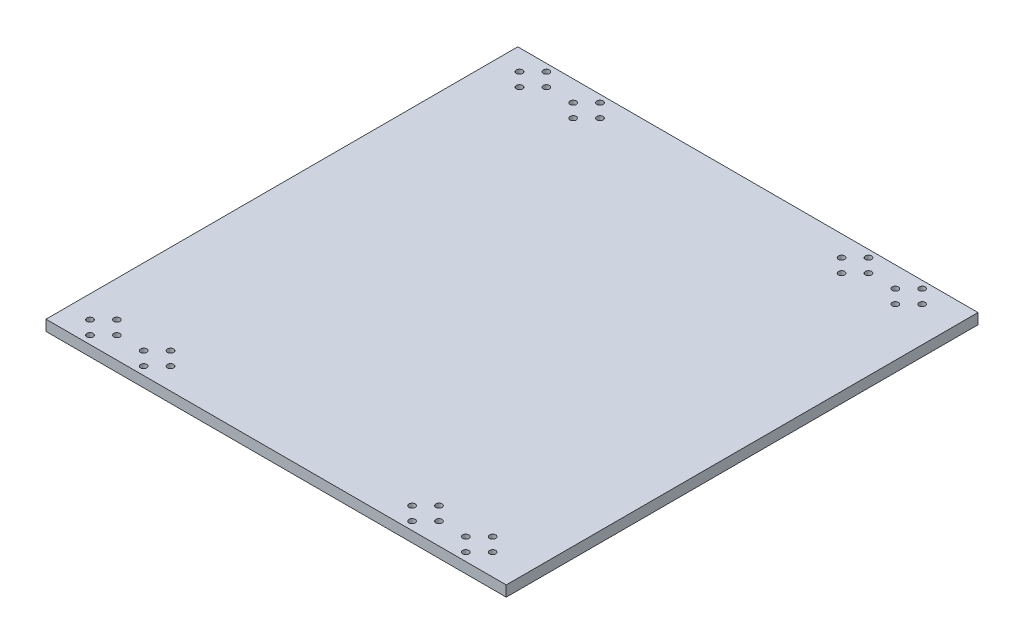
SolidWorks part; units mm, degrees
ref_plane "Front Plane" through (0, 0, 0) normal (0, 0, 1) x (1, 0, 0)
ref_plane "Top Plane" through (0, 0, 0) normal (0, 1, 0) x (1, 0, 0)
ref_plane "Right Plane" through (0, 0, 0) normal (1, 0, 0) x (0, 0, -1)
sketch "Sketch1" plane through (0, 0, 0) normal (0, 1, 0) x (1, 0, 0)
  line L1 (-132.0925, 92.3972) -> (142.2275, 92.3972)
  line L2 (-132.0925, 92.3972) -> (-132.0925, -195.6388)
  line L3 (-132.0925, -195.6388) -> (142.2275, -195.6388)
  line L4 (142.2275, 92.3972) -> (142.2275, -195.6388)
  dimension "D1" = 274.32
  dimension "D2" = 288.036
extrude "Boss-Extrude1" add sketch "Sketch1" along normal blind 6.35
sketch "Sketch2" plane through (0, 0, 0) normal (0, -1, 0) x (1, 0, 0)
  circle A0 centre (121.2775, -76.3612) radius 1.85 construction
  circle A1 centre (105.2775, -76.3612) radius 1.85 construction
  circle A2 centre (113.2775, -84.3612) radius 1.85 construction
  circle A3 centre (113.2775, -68.3612) radius 1.85 construction
  circle A4 centre (121.2775, -76.3612) radius 1.85
  circle A5 centre (105.2775, -76.3612) radius 1.85
  circle A6 centre (113.2775, -84.3612) radius 1.85
  circle A7 centre (113.2775, -68.3612) radius 1.85
  circle A8 centre (89.2775, -76.3612) radius 1.85 construction
  circle A9 centre (89.2775, -76.3612) radius 1.85
  circle A10 centre (81.2775, -84.3612) radius 1.85 construction
  circle A11 centre (81.2775, -84.3612) radius 1.85
  circle A12 centre (81.2775, -68.3612) radius 1.85 construction
  circle A13 centre (81.2775, -68.3612) radius 1.85
  circle A14 centre (73.2775, -76.3612) radius 1.85 construction
  circle A15 centre (73.2775, -76.3612) radius 1.85
  circle A16 centre (-86.7225, -76.3612) radius 1.85 construction
  circle A17 centre (-118.7225, -76.3612) radius 1.85 construction
  circle A18 centre (-110.7225, -84.3612) radius 1.85 construction
  circle A19 centre (-102.7225, -76.3612) radius 1.85 construction
  circle A20 centre (-110.7225, -68.3612) radius 1.85 construction
  circle A21 centre (-86.7225, -76.3612) radius 1.85
  circle A22 centre (-118.7225, -76.3612) radius 1.85
  circle A23 centre (-110.7225, -84.3612) radius 1.85
  circle A24 centre (-102.7225, -76.3612) radius 1.85
  circle A25 centre (-110.7225, -68.3612) radius 1.85
  circle A26 centre (-70.7225, -76.3612) radius 1.85 construction
  circle A27 centre (-78.7225, -68.3612) radius 1.85 construction
  circle A28 centre (-78.7225, -84.3612) radius 1.85 construction
  circle A29 centre (-86.7225, -76.3612) radius 1.85
  circle A30 centre (-70.7225, -76.3612) radius 1.85
  circle A31 centre (-78.7225, -68.3612) radius 1.85
  circle A32 centre (-78.7225, -84.3612) radius 1.85
  circle A33 centre (73.2775, 179.6388) radius 1.85 construction
  circle A34 centre (81.2775, 187.6388) radius 1.85 construction
  circle A35 centre (81.2775, 171.6388) radius 1.85 construction
  circle A36 centre (89.2775, 179.6388) radius 1.85 construction
  circle A37 centre (105.2775, 179.6388) radius 1.85 construction
  circle A38 centre (113.2775, 187.6388) radius 1.85 construction
  circle A39 centre (121.2775, 179.6388) radius 1.85 construction
  circle A40 centre (113.2775, 171.6388) radius 1.85 construction
  circle A41 centre (73.2775, 179.6388) radius 1.85
  circle A42 centre (81.2775, 187.6388) radius 1.85
  circle A43 centre (81.2775, 171.6388) radius 1.85
  circle A44 centre (89.2775, 179.6388) radius 1.85
  circle A45 centre (105.2775, 179.6388) radius 1.85
  circle A46 centre (113.2775, 187.6388) radius 1.85
  circle A47 centre (121.2775, 179.6388) radius 1.85
  circle A48 centre (113.2775, 171.6388) radius 1.85
  circle A49 centre (-70.7225, 179.6388) radius 1.85 construction
  circle A50 centre (-78.7225, 187.6388) radius 1.85 construction
  circle A51 centre (-78.7225, 171.6388) radius 1.85 construction
  circle A52 centre (-86.7225, 179.6388) radius 1.85 construction
  circle A53 centre (-102.7225, 179.6388) radius 1.85 construction
  circle A54 centre (-110.7225, 187.6388) radius 1.85 construction
  circle A55 centre (-118.7225, 179.6388) radius 1.85 construction
  circle A56 centre (-110.7225, 171.6388) radius 1.85 construction
  circle A57 centre (-70.7225, 179.6388) radius 1.85
  circle A58 centre (-78.7225, 187.6388) radius 1.85
  circle A59 centre (-78.7225, 171.6388) radius 1.85
  circle A60 centre (-86.7225, 179.6388) radius 1.85
  circle A61 centre (-102.7225, 179.6388) radius 1.85
  circle A62 centre (-110.7225, 187.6388) radius 1.85
  circle A63 centre (-118.7225, 179.6388) radius 1.85
  circle A64 centre (-110.7225, 171.6388) radius 1.85
extrude "Cut-Extrude1" cut sketch "Sketch2" against normal up to next contours A22 | A23 | A25 | A24 | A21 | A31 | A32 | A30
extrude "Cut-Extrude2" cut sketch "Sketch2<5>" against normal up to next contours A15 | A13 | A11 | A9 | A5 | A7 | A4 | A6 | A42 | A41 | A43 | A44 | A45 | A46 | A48 | A47 | A63 | A64 | A62 | A61 | A60 | A58 | A59 | A57
sketch "Sketch2<5>" plane through (0, 0, 0) normal (0, -1, 0) x (1, 0, 0) same geometry as "Sketch2"
sketch "Sketch3" plane through (0, 0, 0) normal (0, -1, 0) x (1, 0, 0)
  line L0 (142.2275, 195.6388) -> (142.2275, -92.3972) construction
  line L1 (-132.0925, 195.6388) -> (142.2275, 195.6388)
  line L2 (-132.0925, 195.6388) -> (-132.0925, 192.4927)
  line L3 (-132.0925, 192.4927) -> (142.2275, 192.4927)
  line L4 (142.2275, 195.6388) -> (142.2275, 192.4927)
  line L6 (-132.0925, -92.3972) -> (142.2275, -92.3972)
  line L7 (-132.0925, -92.3972) -> (-132.0925, -88.7015)
  line L8 (-132.0925, -88.7015) -> (142.2275, -88.7015)
  line L9 (142.2275, -92.3972) -> (142.2275, -88.7015)
  point P12 (0, 0)
extrude "Cut-Extrude3" cut sketch "Sketch3" against normal up to next
